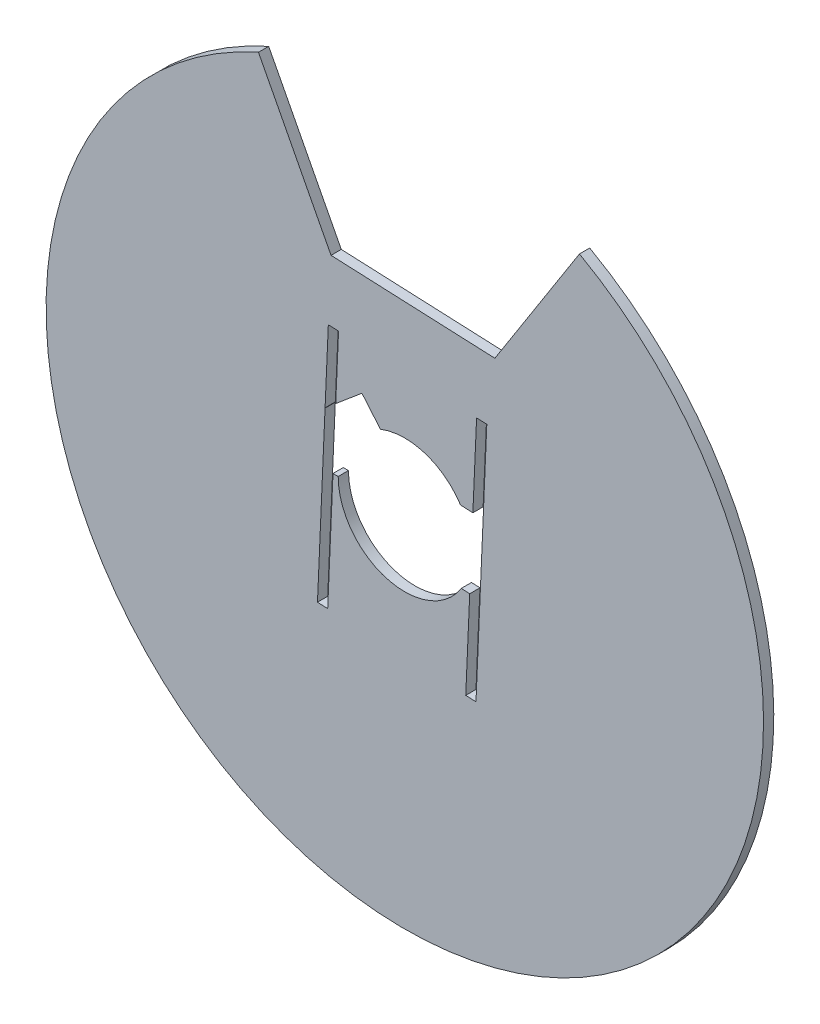
SolidWorks part; units mm, degrees
material "Balsa"
ref_plane "Plan de face" through (0, 0, 0) normal (0, 0, 1) x (1, 0, 0)
ref_plane "Plan de dessus" through (0, 0, 0) normal (0, 1, 0) x (1, 0, 0)
ref_plane "Plan de droite" through (0, 0, 0) normal (1, 0, 0) x (0, 0, -1)
sketch "Esquisse1" plane through (0, 0, 0) normal (0, 0, 1) x (1, 0, 0)
  line L0 (-11.9, 30.243) -> (-20.9197, 40.9503)
  line L1 (0, 0) -> (31.6699, 0) construction
  line L2 (-20.9197, 40.9503) -> (-33.7021, 30.1824)
  line L4 (0, 0) -> (0, 32.5) construction
  line L5 (35.6001, -41.61) -> (34.7183, -61.5906) construction
  line L6 (-41.7246, -38.1976) -> (-36.7295, -38.418) construction
  line L7 (-41.7246, -38.1976) -> (-41.2837, -28.2073) construction
  line L8 (-41.2837, -28.2073) -> (-36.2886, -28.4277) construction
  line L9 (-36.7295, -38.418) -> (-36.2886, -28.4277) construction
  line L10 (34.7183, -61.5906) -> (40.0089, 58.2928)
  line L11 (-38.9773, 25.7386) -> (-11.9, 30.243) construction
  line L12 (-29.9576, 15.0314) -> (-20.9197, 40.9503) construction
  line L13 (0, 0) -> (-25.4386, 27.9908) construction
  line L14 (34.7183, -61.5906) -> (29.7232, -61.3701)
  line L15 (40.0089, 58.2928) -> (35.0138, 58.5132)
  line L16 (30.605, -41.3896) -> (35.6001, -41.61) construction
  line L17 (30.605, -41.3896) -> (31.0459, -31.3993) construction
  line L18 (35.6001, -41.61) -> (36.041, -31.6197) construction
  line L19 (31.0459, -31.3993) -> (36.041, -31.6197) construction
  line L20 (29.7232, -61.3701) -> (31.6607, -17.466)
  line L21 (-37.6113, -58.3986) -> (-42.6064, -58.1781)
  line L22 (-37.6113, -58.3986) -> (-35.0341, 0)
  line L23 (-42.6064, -58.1781) -> (-37.3158, 61.7052)
  line L24 (39.1272, 38.3122) -> (34.132, 38.5327) construction
  line L25 (39.1272, 38.3122) -> (38.6863, 28.3219) construction
  line L26 (34.132, 38.5327) -> (33.6911, 28.5424) construction
  line L27 (38.6863, 28.3219) -> (33.6911, 28.5424) construction
  line L28 (-32.3207, 61.4847) -> (-37.3158, 61.7052)
  line L29 (-38.9068, 25.6548) -> (-38.9773, 25.7386)
  line L30 (-38.9002, 25.8036) -> (-38.9773, 25.7386)
  line L31 (-33.7021, 30.1824) -> (-32.3207, 61.4847)
  line L32 (-33.2024, 41.5042) -> (-38.1976, 41.7246) construction
  line L33 (-33.2024, 41.5042) -> (-33.6433, 31.5139) construction
  line L34 (-38.1976, 41.7246) -> (-38.6385, 31.7344) construction
  line L35 (-33.6433, 31.5139) -> (-38.6385, 31.7344) construction
  line L36 (33.2038, 17.5) -> (35.0138, 58.5132)
  line L37 (-32.5, 0) -> (-35.0341, 0)
  line L38 (27.2154, 17.7643) -> (33.2038, 17.5)
  line L39 (27.5233, -17.2834) -> (31.6607, -17.466)
  line L40 (-38.1976, 41.7246) -> (39.1272, 38.3122) construction
  line L41 (-38.1976, 41.7246) -> (-41.7246, -38.1976) construction
  line L42 (39.1272, 38.3122) -> (35.6001, -41.61) construction
  line L43 (-41.7246, -38.1976) -> (35.6001, -41.61) construction
  circle A0 centre (0, 0) radius 175
  arc A1 (-32.5, 0) -> (27.5233, -17.2834) centre (0, 0) ccw
  arc A2 (27.2154, 17.7643) -> (-11.9, 30.243) centre (0, 0) ccw
  dimension "D1" = 65
  dimension "D10" = 350
  dimension "D2" = 87.845
  dimension "D3" = 42.265
  dimension "D4" = 14
  dimension "D5" = 10
  dimension "D6" = 57.18
  dimension "D7" = 5
  dimension "D8" = 20
  dimension "D9" = 20
  dimension "D11" = 35
  dimension "D12" = 17.5
extrude "Boss.-Extru.1" add sketch "Esquisse1" along normal blind 5 contours A0 A2 L36 L15 L10 L14 L20 A1 L22 L21 L23 L29 L30 L28 L31 L2 L0 region at (-170.0503, 0, 0)
sketch "Esquisse2" plane through (0, 0, 5) normal (0, 0, 1) x (1, 0, 0)
  line L0 (43.929, 88.149) -> (85.1976, 152.8606)
  line L1 (43.929, 88.149) -> (-35.9932, 91.676)
  line L2 (-35.9932, 91.676) -> (-71.4008, 159.7715)
  line L3 (-71.4008, 159.7715) -> (-35.9932, 91.676) construction
  line L4 (43.929, 88.149) -> (85.1976, 152.8606) construction
  circle A0 centre (0, 0) radius 175 construction
  arc A1 (85.1976, 152.8606) -> (-71.4008, 159.7715) centre (0, 0) ccw
extrude "Enlèv. mat.-Extru.1" cut sketch "Esquisse2" against normal blind 10
